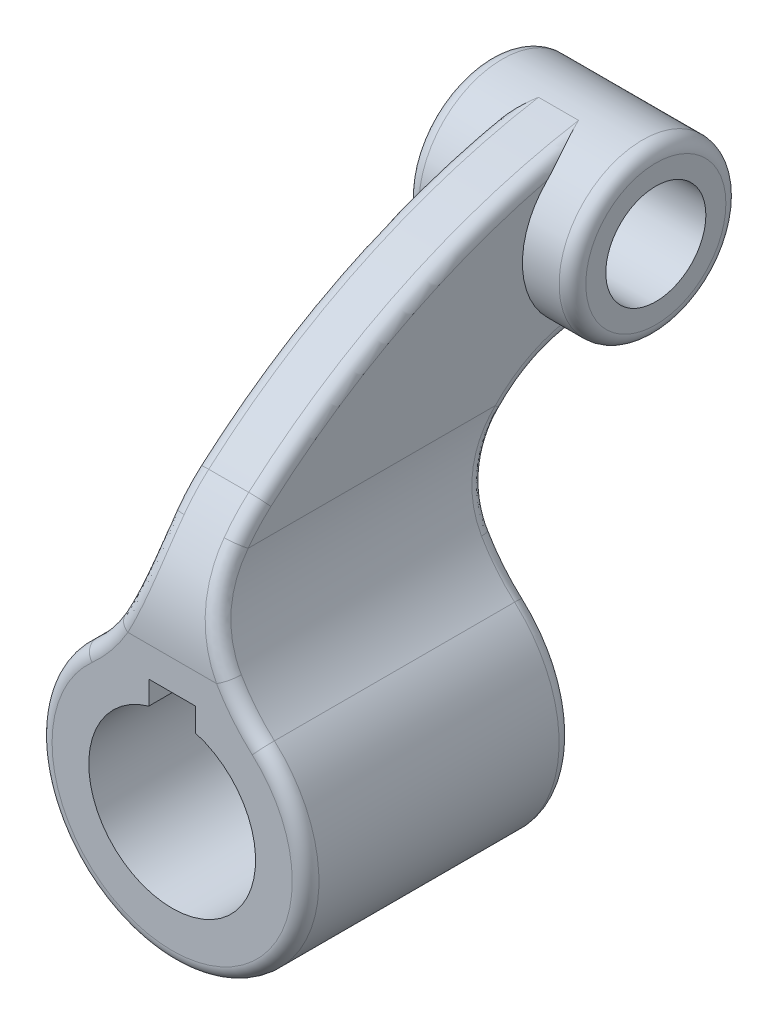
SolidWorks part; units mm, degrees
ref_plane "前基準面" through (0, 0, 0) normal (0, 0, 1) x (1, 0, 0)
ref_plane "上基準面" through (0, 0, 0) normal (0, 1, 0) x (1, 0, 0)
ref_plane "右基準面" through (0, 0, 0) normal (1, 0, 0) x (0, 0, -1)
sketch "草圖1" plane through (0, 0, 0) normal (0, 0, 1) x (1, 0, 0)
  line L0 (0, 10.7834) -> (0, -8.8536) construction
  line L1 (-7, -24) -> (7, -24)
  line L2 (-7, -24) -> (-7, 31)
  line L3 (-7, 31) -> (7, 31)
  line L4 (7, -24) -> (7, 31)
  circle A0 centre (0, 0) radius 40
  arc A1 (-7, 24) -> (7, 24) centre (0, 0) ccw
  dimension "D1" = 80
  dimension "D2" = 50
  dimension "D3" = 14
  dimension "D4" = 55
extrude "填料-伸長1" add sketch "草圖1" along normal mid plane 80 contours A0 A1 L2 L3 L4 region at (-38.8686, 0, 0)
sketch "草圖2" plane through (0, 0, 0) normal (1, 0, 0) x (0, 0, -1)
  line L0 (-53.3766, 0) -> (59.5959, 0) construction
  line L1 (40, -40) -> (40, 40) construction
  line L2 (40, 40) -> (-40, 40) construction
  line L4 (-40, 40) -> (-40, 36.7064)
  line L5 (-40, 40) -> (-40, -40) construction
  line L6 (-40, 36.7064) -> (40, 36.7064)
  line L7 (40, 36.7064) -> (40, 40)
  arc A0 (78.0032, 75.0799) -> (75.8352, 124.6506) centre (80, 100) ccw construction
  arc A1 (40, 40) -> (78.0032, 75.0799) centre (75.1923, 40) cw
  arc A2 (-40, 40) -> (-23.0513, 77.5182) centre (10, 40) cw
  arc A3 (-23.0513, 77.5182) -> (75.8352, 124.6506) centre (109.1539, -72.5545) cw
  arc A4 (78.0032, 75.0799) -> (75.8352, 124.6506) centre (80, 100) cw
  dimension "D1" = 100
  dimension "D2" = 40
  dimension "D3" = 50
  dimension "D4" = 50
  dimension "D5" = 200
  dimension "D6" = 3.2936
extrude "填料-伸長2" add sketch "草圖2" along normal mid plane 20
sketch "草圖4" plane through (0, 0, 0) normal (1, 0, 0) x (0, 0, -1)
  circle A0 centre (80, 100) radius 15
  circle A1 centre (80, 100) radius 25
  dimension "D1" = 50
  dimension "D2" = 30
extrude "填料-伸長3" add sketch "草圖4" along normal mid plane 50
fillet "圓角9" radius 50 2 edges at (-10, 38.7298, 0) (10, 38.7298, 0)
fillet "圓角14" radius 4 18 edges at (10, 107.9866, -23.1021) (10, 72.6106, 27.9018) (12.4898, 51.5005, 38.6594) (21.9755, 34.6146, 40) (0, -40, 40) (-21.9755, 34.6146, 40) (-11.3406, 55.5815, 37.5102) (-10, 72.6106, 27.9018) (-10, 107.9866, -23.1021) (-10, 73.5537, -64.5788) (-13.2413, 49.3727, -41.271) (-21.9755, 34.6146, -40) (10, 73.5537, -64.5788) (10.6274, 59.186, -45.6898) (21.9755, 34.6146, -40) (0, -40, -40) (-25, 100, -105) (25, 100, -105)
